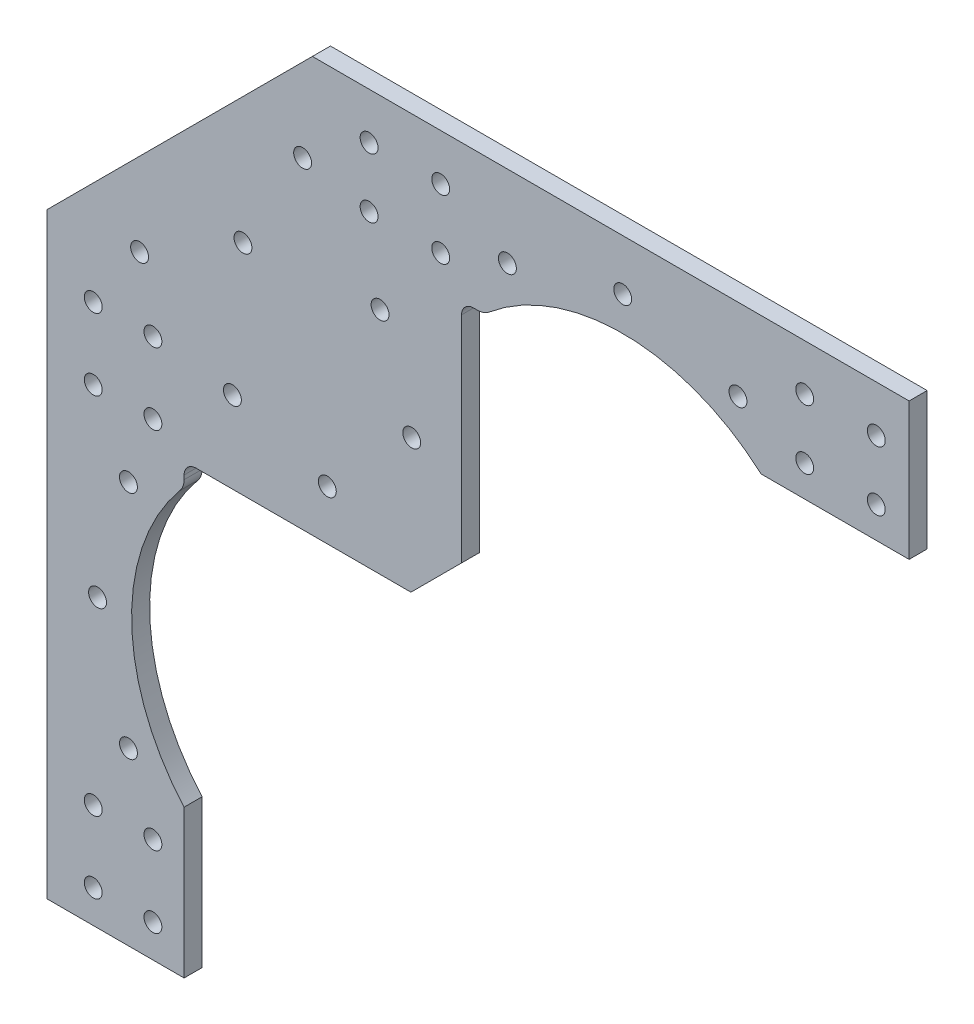
SolidWorks part; units mm, degrees
ref_plane "Front Plane" through (0, 0, 0) normal (0, 0, 1) x (1, 0, 0)
ref_plane "Top Plane" through (0, 0, 0) normal (0, 1, 0) x (1, 0, 0)
ref_plane "Right Plane" through (0, 0, 0) normal (1, 0, 0) x (0, 0, -1)
sketch "Sketch1" plane through (0, 0, 0) normal (0, 0, 1) x (1, 0, 0)
  line L0 (0, 0) -> (0, 73.5) construction
  line L1 (-96.5, -48) -> (-73.5, -48)
  line L2 (-96.5, -48) -> (-96.5, 52)
  line L4 (-73.5, -48) -> (-73.5, 27) construction
  line L5 (-52, 96.5) -> (48, 96.5)
  line L7 (-27, 73.5) -> (48, 73.5) construction
  line L8 (48, 96.5) -> (48, 73.5)
  line L9 (0, 0) -> (-73.5, 0) construction
  line L10 (-27, 73.5) -> (-73.5, 27) construction
  line L11 (-73.5, 73.5) -> (-27, 73.5) construction
  line L12 (-73.5, 27) -> (-73.5, 73.5) construction
  line L13 (-52, 96.5) -> (-96.5, 52)
  line L14 (-96.5, 96.5) -> (-52, 96.5) construction
  line L15 (-96.5, 52) -> (-96.5, 96.5) construction
  line L16 (-24.3179, 73.5) -> (-25, 73.5)
  line L17 (23.2069, 73.5) -> (48, 73.5)
  line L18 (-73.5, 25) -> (-73.5, 24.3179)
  line L19 (-73.5, -48) -> (-73.5, -23.2069)
  line L20 (-73.5, 23.2069) -> (-73.5, -23.2069) construction
  line L21 (-23.2069, 73.5) -> (23.2069, 73.5) construction
  line L22 (-71.5, 27) -> (-35.4853, 27)
  line L23 (-27, 35.4853) -> (-27, 71.5)
  line L24 (-35.4853, 27) -> (-27, 35.4853)
  line L25 (-25, 73.5) -> (-27, 73.5) construction
  line L26 (-27, 71.5) -> (-27, 73.5) construction
  line L27 (-73.5, 27) -> (-73.5, 25) construction
  line L28 (-73.5, 27) -> (-71.5, 27) construction
  line L29 (-23.2069, 73.5) -> (-24.3179, 73.5) construction
  line L30 (-73.5, 24.3179) -> (-73.5, 23.2069) construction
  arc A0 (23.2069, 73.5) -> (-22.3981, 74.1947) centre (0, 47.3) ccw
  arc A1 (-74.1947, 22.3981) -> (-73.5, -23.2069) centre (-47.3, 0) ccw
  arc A2 (-25, 73.5) -> (-27, 71.5) centre (-25, 71.5) ccw
  arc A3 (-71.5, 27) -> (-73.5, 25) centre (-71.5, 25) ccw
  arc A4 (-24.3179, 73.5) -> (-22.3981, 74.1947) centre (-24.3179, 76.5) ccw
  arc A5 (-22.3981, 74.1947) -> (-23.2069, 73.5) centre (0, 47.3) ccw construction
  arc A6 (-73.5, 24.3179) -> (-74.1947, 22.3981) centre (-76.5, 24.3179) cw
  arc A7 (-73.5, 23.2069) -> (-74.1947, 22.3981) centre (-47.3, 0) ccw construction
  dimension "D6" = 35
  dimension "D10" = 2
  dimension "D11" = 3
  dimension "D1" = 135
  dimension "D2" = 23
  dimension "D3" = 73.5
  dimension "D4" = 48
  dimension "D8" = 27
  dimension "D9" = 12
  dimension "D5" = 100
  dimension "D7" = 26.2
extrude "Boss-Extrude1" add sketch "Sketch1" along normal blind 3.0226
ref_axis "Axis1" through (0, 0, -0.1511) along (0, 0, 1)
sketch "Sketch3" plane through (0, 0, 3.0226) normal (0, 0, 1) x (1, 0, 0)
  line L1 (30.5, 88.7259) -> (30.5, 78.7259) construction
  line L2 (30.5, 88.7259) -> (42.5, 88.7259) construction
  line L3 (42.5, 88.7259) -> (42.5, 78.7259) construction
  line L4 (30.5, 78.7259) -> (42.5, 78.7259) construction
  line L16 (-30.5, 78.7259) -> (0, 78.7259) construction
  line L17 (0, 78.7259) -> (0, 0) construction
  line L18 (0, 78.7259) -> (30.5, 78.7259) construction
  line L19 (-78.7259, 0) -> (0, 0) construction
  line L20 (-78.7259, -30.5) -> (-78.7259, 0) construction
  line L21 (-78.7259, 0) -> (-78.7259, 30.5) construction
  line L30 (-42.5, 88.7259) -> (-42.5, 78.7259) construction
  line L31 (-42.5, 88.7259) -> (-30.5, 88.7259) construction
  line L32 (-30.5, 88.7259) -> (-30.5, 78.7259) construction
  line L33 (-42.5, 78.7259) -> (-30.5, 78.7259) construction
  line L34 (-88.7259, 42.5) -> (-88.7259, 30.5) construction
  line L35 (-88.7259, 42.5) -> (-78.7259, 42.5) construction
  line L36 (-78.7259, 42.5) -> (-78.7259, 30.5) construction
  line L37 (-88.7259, 30.5) -> (-78.7259, 30.5) construction
  line L38 (-88.7259, -30.5) -> (-88.7259, -42.5) construction
  line L39 (-88.7259, -30.5) -> (-78.7259, -30.5) construction
  line L40 (-78.7259, -30.5) -> (-78.7259, -42.5) construction
  line L41 (-88.7259, -42.5) -> (-78.7259, -42.5) construction
  circle A0 centre (30.5, 78.7259) radius 1.5
  circle A1 centre (30.5, 88.7259) radius 1.5
  circle A2 centre (42.5, 88.7259) radius 1.5
  circle A3 centre (42.5, 78.7259) radius 1.5
  circle A24 centre (-42.5, 78.7259) radius 1.5
  circle A25 centre (-42.5, 88.7259) radius 1.5
  circle A26 centre (-30.5, 88.7259) radius 1.5
  circle A27 centre (-30.5, 78.7259) radius 1.5
  circle A28 centre (-88.7259, 30.5) radius 1.5
  circle A29 centre (-88.7259, 42.5) radius 1.5
  circle A30 centre (-78.7259, 42.5) radius 1.5
  circle A31 centre (-78.7259, 30.5) radius 1.5
  circle A32 centre (-88.7259, -42.5) radius 1.5
  circle A33 centre (-88.7259, -30.5) radius 1.5
  circle A34 centre (-78.7259, -30.5) radius 1.5
  circle A35 centre (-78.7259, -42.5) radius 1.5
  dimension "D1" = 3
  dimension "D8" = 30.5
  dimension "D2" = 12
  dimension "D6" = 10
  dimension "D3" = 78.7259
extrude "Cut-Extrude1" cut sketch "Sketch3" against normal blind 10
sketch "Sketch4" plane through (0, 0, 3.0226) normal (0, 0, 1) x (1, 0, 0)
  line L0 (0, 0) -> (0, 88) construction
  line L1 (0, 0) -> (-63.6396, 63.6396) construction
  line L2 (0, 0) -> (-88, 0) construction
  line L3 (-82.8236, 19.3185) -> (-88, 0) construction
  line L4 (-88, 0) -> (-82.8236, -19.3185) construction
  line L5 (-80.9601, 53.6396) -> (-63.6396, 63.6396) construction
  line L6 (-63.6396, 63.6396) -> (-83.2677, 83.2677) construction
  line L7 (-19.3185, 82.8236) -> (0, 88) construction
  line L8 (-65.4074, 40.6586) -> (-40.6586, 65.4074) construction
  line L9 (-35.3553, 49.4975) -> (-49.4975, 35.3553) construction
  line L10 (-73.5, -48) -> (-73.5, -23.2069) construction
  line L11 (-35.4853, 27) -> (-27, 35.4853) construction
  circle A0 centre (-88, 0) radius 1.5
  circle A1 centre (-63.6396, 63.6396) radius 1.5
  circle A2 centre (0, 88) radius 1.5
  circle A3 centre (-80.9601, 53.6396) radius 1.5
  circle A4 centre (-53.6396, 80.9601) radius 1.5
  circle A5 centre (19.3185, 82.8236) radius 1.5
  circle A6 centre (-19.3185, 82.8236) radius 1.5
  circle A7 centre (-82.8236, 19.3185) radius 1.5
  circle A8 centre (-82.8236, -19.3185) radius 1.5
  circle A9 centre (-40.6586, 65.4074) radius 1.5
  circle A10 centre (-65.4074, 40.6586) radius 1.5
  circle A11 centre (-49.4975, 35.3553) radius 1.5
  circle A12 centre (-35.3553, 49.4975) radius 1.5
  dimension "D2" = 3
  dimension "D1" = 45
  dimension "D3" = 14.5
  dimension "D4" = 75
  dimension "D5" = 20
  dimension "D6" = 45.8162
  dimension "D7" = 75
  dimension "D8" = 75
  dimension "D9" = 35
  dimension "D10" = 20
  dimension "D11" = 15
  dimension "D12" = 15
extrude "Cut-Extrude2" cut sketch "Sketch4" against normal through all
equation "\"EyeDiameter\" = 35"
equation "\"BasePlaneDistance\" = \"EyeDiameter\"/2+19.84"
equation "\"EyeClearance\" = 2"
equation "\"L2Thickness\" = 8"
equation "\"L2_ID\" = 20"
equation "\"Offset\"= - 2"
equation "\"D3@Sketch1\"=\"BasePlaneDistance\" + 38.16 +\"Offset\""
equation "\"D3@Sketch3\"=\"BasePlaneDistance\" - 37.34+78.72592343"
equation "\"D7@Sketch1\"=24.20 - \"Offset\""
equation "\"D2@Sketch1\"=25.00 + \"Offset\""
